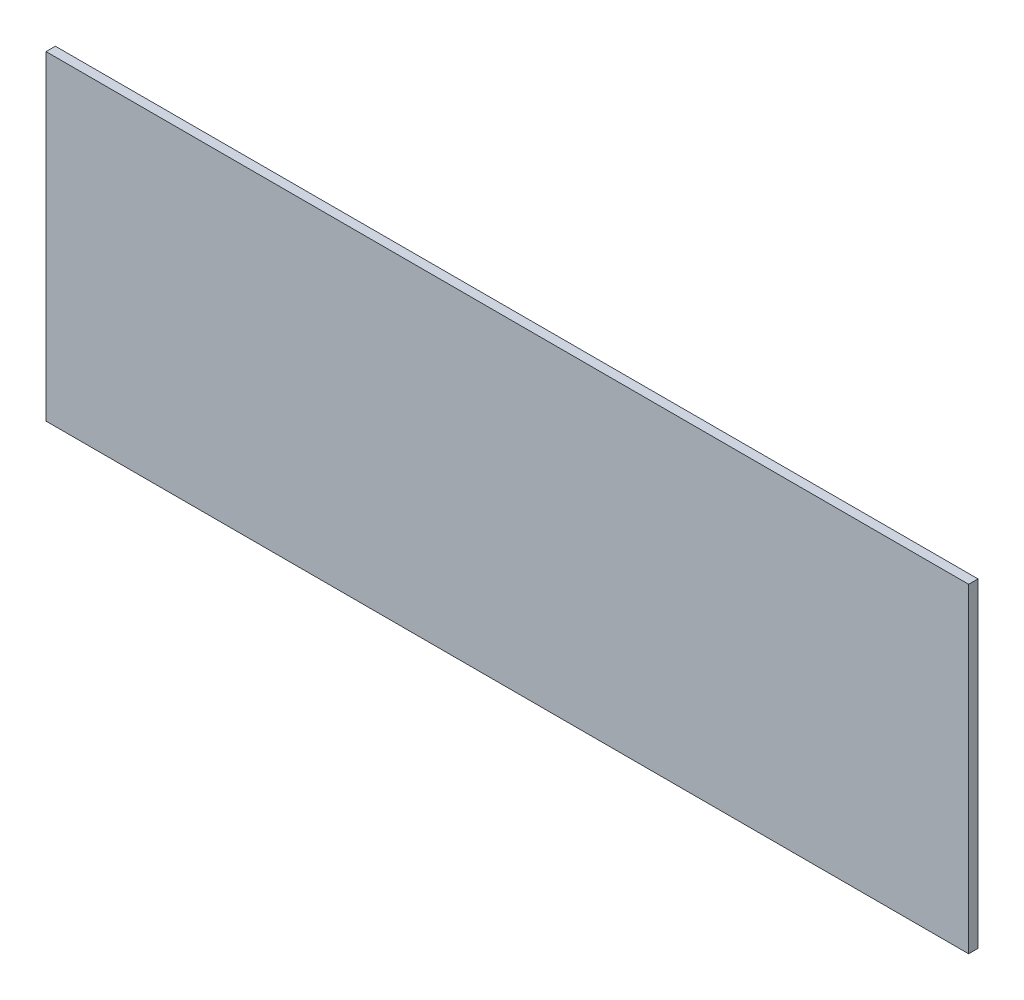
SolidWorks part; units mm, degrees
material "E-Glass Fiber"
ref_plane "Front Plane" through (0, 0, 0) normal (0, 0, 1) x (1, 0, 0)
ref_plane "Top Plane" through (0, 0, 0) normal (0, 1, 0) x (1, 0, 0)
ref_plane "Right Plane" through (0, 0, 0) normal (1, 0, 0) x (0, 0, -1)
sketch "Sketch1" plane through (0, 0, 0) normal (0, 0, 1) x (1, 0, 0)
  line L1 (-117.475, -40.7479) -> (117.475, -40.7479)
  line L2 (-117.475, -40.7479) -> (-117.475, 40.748)
  line L3 (-117.475, 40.748) -> (117.475, 40.748)
  line L4 (117.475, -40.7479) -> (117.475, 40.748)
  line L5 (-117.475, -40.7479) -> (117.475, 40.748) construction
  line L6 (-117.475, 40.748) -> (117.475, -40.7479) construction
  point P0 (0, 0)
  dimension "D1" = 234.95
  dimension "D2" = 81.4959
extrude "Boss-Extrude1" add sketch "Sketch1" along normal blind 2.3813
